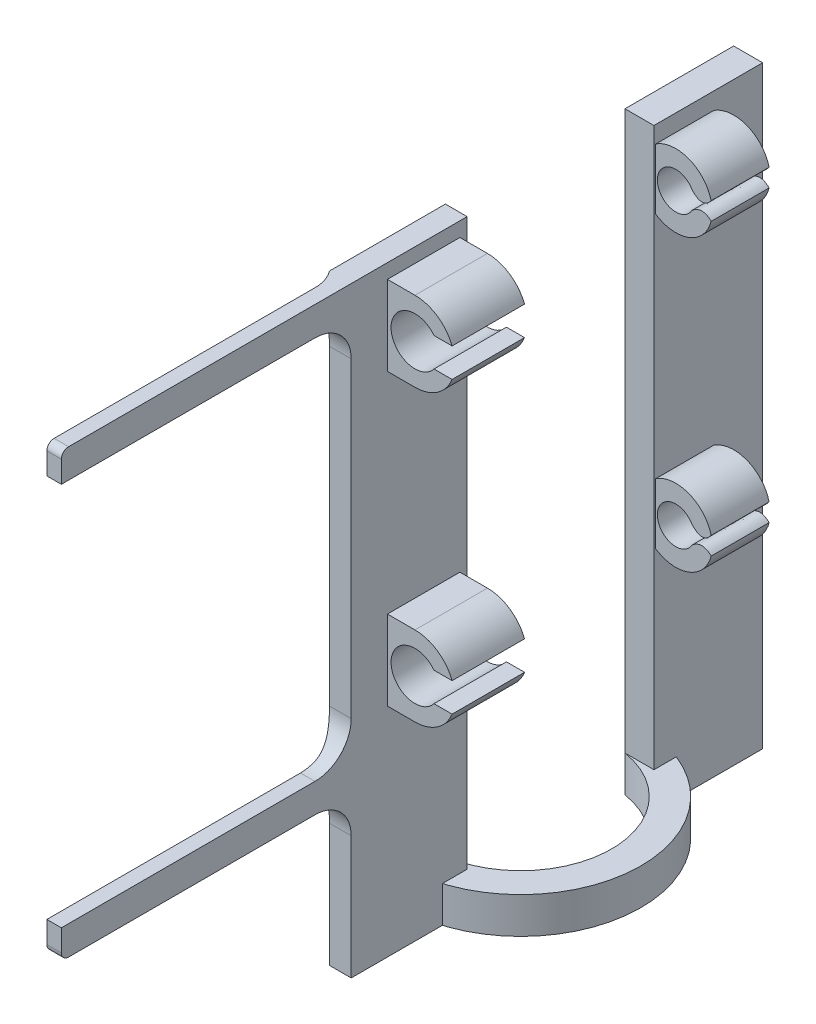
SolidWorks part; units mm, degrees
ref_plane "Front Plane" through (0, 0, 0) normal (0, 0, 1) x (1, 0, 0)
ref_plane "Top Plane" through (0, 0, 0) normal (0, 1, 0) x (1, 0, 0)
ref_plane "Right Plane" through (0, 0, 0) normal (1, 0, 0) x (0, 0, -1)
sketch "Sketch1" plane through (0, 0, 0) normal (0, 0, 1) x (1, 0, 0)
  line L0 (0, 5.5) -> (-3.7992, 5.5)
  line L1 (-3.7992, 5.5) -> (-3.7992, -5.5)
  line L2 (-3.7992, -5.5) -> (0, -5.5)
  line L3 (-20.8389, -20) -> (24.3467, -20) construction
  line L4 (2.6249, 2) -> (5.1235, 2)
  line L5 (2.6249, -2) -> (5.1235, -2)
  line L6 (2.6249, -38) -> (5.1235, -38)
  line L7 (2.6249, -42) -> (5.1235, -42)
  line L8 (-3.7992, -34.5) -> (0, -34.5)
  line L9 (-3.7992, -45.5) -> (-3.7992, -34.5)
  line L10 (0, -45.5) -> (-3.7992, -45.5)
  arc A0 (2.6249, 2) -> (2.6249, -2) centre (0, 0) ccw
  arc A1 (0, -5.5) -> (5.1235, -2) centre (0, 0) ccw
  arc A2 (5.1235, 2) -> (0, 5.5) centre (0, 0) ccw
  arc A3 (5.1235, -42) -> (0, -45.5) centre (0, -40) cw
  arc A4 (0, -34.5) -> (5.1235, -38) centre (0, -40) cw
  arc A5 (2.6249, -42) -> (2.6249, -38) centre (0, -40) cw
  dimension "D1" = 6.6
  dimension "D2" = 11
  dimension "D3" = 20
  dimension "D4" = 2
  dimension "D5" = 2
extrude "Boss-Extrude1" add sketch "Sketch1" along normal blind 10
sketch "Sketch2" plane through (-3.7992, 0, 0) normal (-1, 0, 0) x (0, 0, 1)
  line L0 (0, 5.5) -> (0, -5.5) construction
  line L1 (-1, 7.5) -> (15, 7.5)
  line L2 (-1, 7.5) -> (-1, -55.5)
  line L3 (-1, -55.5) -> (15, -55.5)
  line L4 (15, 7.5) -> (15, -55.5)
  line L5 (10, 5.5) -> (10, -5.5) construction
  line L6 (10, 5.5) -> (0, 5.5) construction
  line L7 (10, -45.5) -> (0, -45.5) construction
  dimension "D1" = 1
  dimension "D2" = 5
  dimension "D3" = 2
  dimension "D4" = 10
extrude "Boss-Extrude2" add sketch "Sketch2" along normal blind 3
ref_plane "Plane1" through (0, -75.5, 0) normal (0, -1, 0) x (-1, 0, 0)
sketch "Sketch3" plane through (0, -75.5, 0) normal (0, -1, 0) x (-1, 0, 0)
  line L1 (6.7992, 1) -> (3.7992, 1)
  line L2 (6.7992, 1) -> (6.7992, -15)
  line L3 (6.7992, -15) -> (3.7992, -15)
  line L4 (3.7992, 1) -> (3.7992, -15)
  dimension "D1" = 3
loft "Loft1" add profiles "Sketch3" section face at (-5.2992, -55.5, 7) section "Sketch3"
sketch "Sketch4" plane through (0, -75.5, 0) normal (0, -1, 0) x (1, 0, 0)
  line L0 (-6.7992, 15) -> (-6.7992, -1) construction
  line L2 (-6.7992, 3.0814) -> (-6.7992, -1)
  line L3 (-6.7992, -25.7792) -> (-6.7992, -29.8606)
  arc A0 (-6.7992, -25.7792) -> (-6.7992, -1) centre (-8.7992, -13.3896) ccw
  arc A1 (-6.7992, -29.8606) -> (-6.7992, 3.0814) centre (-8.7992, -13.3896) ccw
  dimension "D1" = 25.1
  dimension "D2" = 2
extrude "Boss-Extrude3" add sketch "Sketch4" against normal blind 5 separate body
sketch "Sketch5" plane through (0, -75.5, 0) normal (0, -1, 0) x (1, 0, 0)
  line L1 (-6.7992, -25.7792) -> (-2.7992, -25.7792)
  line L2 (-6.7992, -25.7792) -> (-6.7992, -40.7792)
  line L3 (-6.7992, -40.7792) -> (-2.7992, -40.7792)
  line L4 (-2.7992, -25.7792) -> (-2.7992, -40.7792)
  dimension "D1" = 4
  dimension "D2" = 15
extrude "Boss-Extrude4" add sketch "Sketch5" against normal blind 82
sketch "Sketch6" plane through (0, 0, 0) normal (0, 0, -1) x (-1, 0, 0)
  circle A0 centre (0, 0) radius 2.55
  dimension "D1" = 5.1
sketch "Sketch7" plane through (0, 0, 0) normal (0, 0, -1) x (-1, 0, 0)
  circle A0 centre (0, 0) radius 5.0297
extrude "Boss-Extrude5" add sketch "Sketch7" along normal blind 8 from offset 26 separate body
extrude "Cut-Extrude1" cut sketch "Sketch6" along normal blind 32
sketch "Sketch8" plane through (0, 0, -32) normal (0, 0, 1) x (1, 0, 0)
  line L0 (4.888, -1.25) -> (6.3067, -1.25)
  line L1 (1.0454, 1.25) -> (2.2226, 1.25)
  line L3 (1.0454, -1.25) -> (2.2226, -1.25)
  line L4 (6.3067, 1.25) -> (6.3067, -1.25)
  line L5 (4.888, 1.25) -> (6.3067, 1.25)
  arc A2 (1.0454, 1.25) -> (1.0454, -1.25) centre (0, 0) ccw
  circle A3 centre (0, 0) radius 2.55 construction
  spline S0 degree 2 poles (4.888, 1.25) (3.6887, -0.3724) (2.2226, 1.25) knots 0 0 0 1 1 1
  spline S1 degree 2 poles (4.888, -1.25) (3.6422, -0.0162) (2.2226, -1.25) knots 0 0 0 1 1 1
  point P1 (6.3067, 0)
  dimension "D1" = 2.5
extrude "Cut-Extrude2" cut sketch "Sketch8" against normal up to surface (2 mm away) and the other way blind 10 up to face at (-5.0297, 0, -34)
pattern_linear "LPattern1" count 2 spacing 40 along (0, -1, 0) of "Boss-Extrude5"
sketch "Sketch9" plane through (0, 0, 15) normal (0, 0, 1) x (1, 0, 0)
  line L0 (-3.7992, -75.5) -> (-3.7992, 7.5) construction
  line L1 (-3.7992, 7.5) -> (-5.7992, 7.5)
  line L2 (-3.7992, 7.5) -> (-3.7992, 3.5)
  line L3 (-3.7992, 3.5) -> (-5.7992, 3.5)
  line L4 (-5.7992, 7.5) -> (-5.7992, 3.5)
  line L5 (-5.7992, -49.5) -> (-3.7992, -49.5)
  line L6 (-5.7992, -49.5) -> (-5.7992, -53.5)
  line L7 (-5.7992, -53.5) -> (-3.7992, -53.5)
  line L8 (-3.7992, -49.5) -> (-3.7992, -53.5)
  dimension "D1" = 2
  dimension "D2" = 4
  dimension "D3" = 2
  dimension "D4" = 4
  dimension "D5" = 53
extrude "Boss-Extrude6" add sketch "Sketch9" along normal blind 40
fillet "Fillet1" radius 5 5 edges at (-5.7992, 5.5, 15) (-5.7992, -51.5, 15) (-4.7992, -49.5, 15) (-4.7992, -53.5, 15) (-4.7992, 3.5, 15)
fillet "Fillet2" radius 1 2 edges at (-4.7992, -53.5, 55) (-4.7992, 7.5, 55)
equation "\"D5@Sketch1\"=\"D4@Sketch1\""
